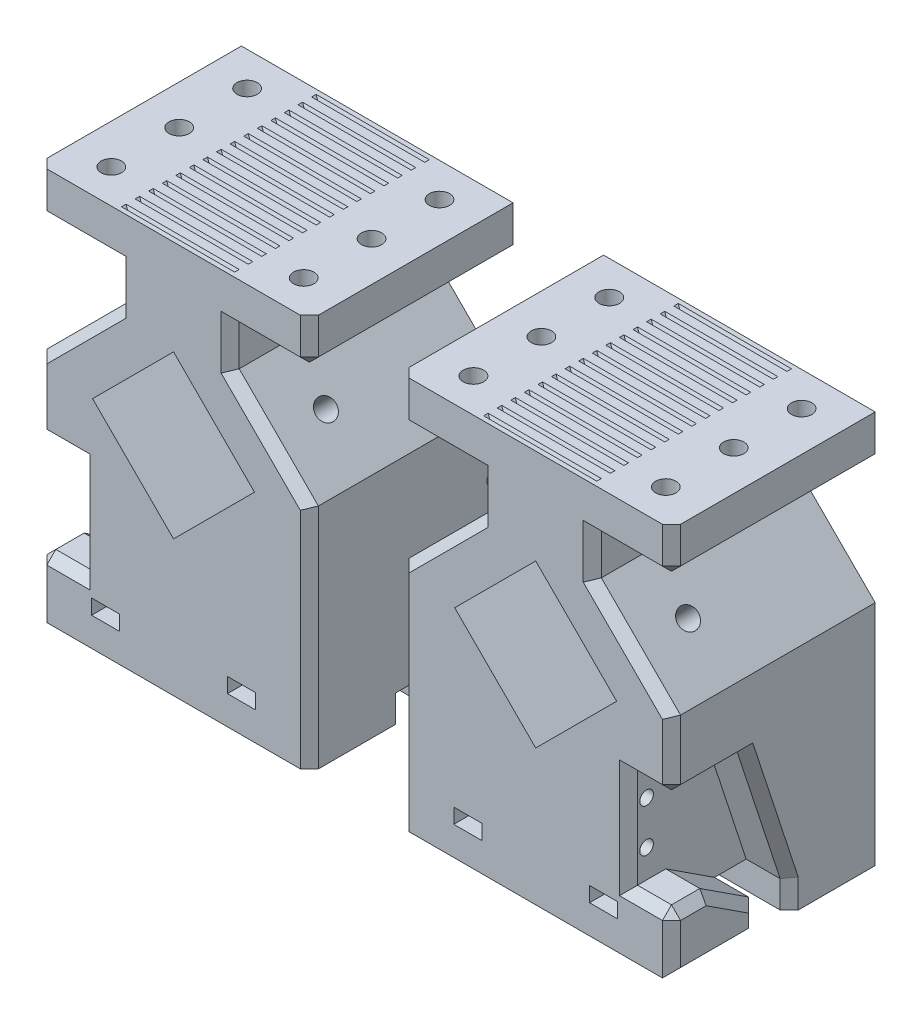
SolidWorks part; units mm, degrees
material "ABS"
ref_plane "Front Plane" through (0, 0, 0) normal (0, 0, 1) x (1, 0, 0)
ref_plane "Top Plane" through (0, 0, 0) normal (0, 1, 0) x (1, 0, 0)
ref_plane "Right Plane" through (0, 0, 0) normal (1, 0, 0) x (0, 0, -1)
sketch "Sketch1" plane through (0, 0, 0) normal (0, 0, 1) x (1, 0, 0)
  line L0 (-30, 25.15) -> (-12.5, 42.65)
  line L2 (30, 25.15) -> (30, -25.15)
  line L3 (30, -25.15) -> (-30, -25.15)
  line L4 (-30, 25.15) -> (-30, -25.15)
  line L5 (30, 25.15) -> (-30, -25.15) construction
  line L6 (30, -25.15) -> (-30, 25.15) construction
  line L7 (30, 25.15) -> (12.5, 42.65)
  line L8 (12.5, 42.65) -> (12.5, 51.65)
  line L9 (-12.5, 42.65) -> (-12.5, 51.65)
  line L10 (-12.5, 51.65) -> (12.5, 51.65) construction
  line L11 (-12.5, 51.65) -> (-30, 51.65)
  line L12 (-30, 51.65) -> (-30, 61.65)
  line L13 (-30, 61.65) -> (30, 61.65)
  line L14 (30, 61.65) -> (30, 51.65)
  line L15 (30, 51.65) -> (12.5, 51.65)
  point P0 (0, 0)
  dimension "D1" = 60
  dimension "D2" = 50.3
  dimension "D3" = 17.5
  dimension "D4" = 17.5
  dimension "D5" = 17.5
  dimension "D6" = 17.5
  dimension "D7" = 9
  dimension "D8" = 10
  dimension "D9" = 25.15
extrude "Boss-Extrude1" add sketch "Sketch1" along normal blind 45
sketch "Sketch2" plane through (0, 0, 45) normal (0, 0, 1) x (1, 0, 0)
  line L0 (0, 40.6296) -> (-17.8898, 22.7398)
  line L1 (-17.8898, 22.7398) -> (0, 4.85)
  line L2 (0, 4.85) -> (17.8898, 22.7398)
  line L3 (17.8898, 22.7398) -> (0, 40.6296)
  line L4 (0, 40.6296) -> (0, 0) construction
  line L5 (-30, -25.15) -> (30, -25.15) construction
  dimension "D1" = 25.3
  dimension "D2" = 25.3
  dimension "D3" = 30
extrude "Cut-Extrude1" cut sketch "Sketch2" against normal blind 25
sketch "Sketch3" plane through (0, -25.15, 0) normal (0, -1, 0) x (1, 0, 0)
  line L0 (-30, 26) -> (30, 26)
  line L1 (-30, 45) -> (-30, 0) construction
  line L2 (30, 45) -> (30, 0) construction
  line L3 (30, 26) -> (30, 19)
  line L4 (30, 19) -> (4.5, 19)
  line L5 (4.5, 19) -> (4.5, 3)
  line L6 (4.5, 3) -> (-4.5, 3)
  line L7 (-4.5, 3) -> (-4.5, 19)
  line L8 (-4.5, 19) -> (-30, 19)
  line L9 (-30, 19) -> (-30, 26)
  line L10 (0, 0) -> (0, 45) construction
  line L11 (-30, 0) -> (30, 0) construction
  line L12 (-30, 45) -> (30, 45) construction
  point P17 (0, 3)
  dimension "D1" = 9
  dimension "D2" = 7
  dimension "D3" = 16
  dimension "D4" = 19
extrude "Cut-Extrude2" cut sketch "Sketch3" against normal blind 6
sketch "Sketch4" plane through (-30, 0, 0) normal (-1, 0, 0) x (0, 0, 1)
  line L0 (45, 25.15) -> (45, -25.15) construction
  line L1 (45, 9.85) -> (28.5, 9.85)
  line L2 (45, 9.85) -> (45, -12.15)
  line L3 (45, -12.15) -> (36.75, -12.15)
  line L5 (45, -25.15) -> (26, -25.15) construction
  line L6 (26, -19.15) -> (36.75, -12.15)
  line L7 (19, -19.15) -> (28.5, 9.85)
  line L8 (26, -19.15) -> (19, -19.15)
  dimension "D1" = 16.5
  dimension "D2" = 13
  dimension "D3" = 22
  dimension "D4" = 8.25
extrude "Cut-Extrude4" cut sketch "Sketch4" against normal blind 9.5
sketch "Sketch5" plane through (0, 0, 0) normal (1, 0, 0) x (0, 0, -1)
  line L0 (-3, -19.15) -> (-3, 9.5665)
  line L1 (-4.0851, 13.008) -> (-11.2085, 23.1813)
  line L2 (-16.1234, 25.7398) -> (-20, 25.7398)
  line L3 (-20, 40.6296) -> (-20, 22.7398) construction
  line L4 (-20, 25.7398) -> (-20, 19.7398)
  line L5 (-20, 22.7398) -> (-20, 4.85) construction
  line L6 (-20, 19.7398) -> (-19.2468, 19.7398)
  line L7 (-14.3319, 17.1813) -> (-10.0851, 11.1162)
  line L8 (-9, 7.6747) -> (-9, -19.15)
  line L9 (-19, -19.15) -> (-3, -19.15) construction
  line L10 (-9, -19.15) -> (-3, -19.15)
  line L11 (-20, 22.7398) -> (-45, 22.7398) construction
  arc A0 (-3, 9.5665) -> (-4.0851, 13.008) centre (-9, 9.5665) ccw
  arc A1 (-10.0851, 11.1162) -> (-9, 7.6747) centre (-15, 7.6747) cw
  arc A2 (-11.2085, 23.1813) -> (-16.1234, 25.7398) centre (-16.1234, 19.7398) ccw
  arc A3 (-19.2468, 19.7398) -> (-14.3319, 17.1813) centre (-19.2468, 13.7398) cw
  point P15 (-19.6234, 19.7398)
  point P24 (-13, 25.7398)
  dimension "D7" = 6
  dimension "D1" = 6
  dimension "D2" = 6
  dimension "D3" = 6
  dimension "D4" = 3
  dimension "D5" = 145
  dimension "D6" = 7
extrude "Cut-Extrude5" cut sketch "Sketch5" against normal mid plane 9
fillet "Fillet1" radius 6 1 edges at (0, -19.15, 9)
ref_plane "Plane1" through (11.5, 0, 0) normal (1, 0, 0) x (0, 0, -1)
sketch "Sketch7" plane through (11.5, 0, 0) normal (1, 0, 0) x (0, 0, -1)
  line L0 (-1, 61.65) -> (-2, 61.65)
  line L1 (-45, 61.65) -> (0, 61.65) construction
  line L2 (-2, 61.65) -> (-1.5, 60.65)
  line L3 (-1.5, 60.65) -> (-1, 61.65)
  line L4 (-1.5, 60.65) -> (-1.5, 61.65) construction
  line L5 (-5, 61.65) -> (-4.5, 60.65)
  line L6 (-4, 61.65) -> (-5, 61.65)
  line L7 (-4.5, 60.65) -> (-4, 61.65)
  line L8 (-8, 61.65) -> (-7.5, 60.65)
  line L9 (-7, 61.65) -> (-8, 61.65)
  line L10 (-7.5, 60.65) -> (-7, 61.65)
  line L11 (-11, 61.65) -> (-10.5, 60.65)
  line L12 (-10, 61.65) -> (-11, 61.65)
  line L13 (-10.5, 60.65) -> (-10, 61.65)
  line L14 (-14, 61.65) -> (-13.5, 60.65)
  line L15 (-13, 61.65) -> (-14, 61.65)
  line L16 (-13.5, 60.65) -> (-13, 61.65)
  line L17 (-17, 61.65) -> (-16.5, 60.65)
  line L18 (-16, 61.65) -> (-17, 61.65)
  line L19 (-16.5, 60.65) -> (-16, 61.65)
  line L20 (-20, 61.65) -> (-19.5, 60.65)
  line L21 (-19, 61.65) -> (-20, 61.65)
  line L22 (-19.5, 60.65) -> (-19, 61.65)
  line L23 (-23, 61.65) -> (-22.5, 60.65)
  line L24 (-22, 61.65) -> (-23, 61.65)
  line L25 (-22.5, 60.65) -> (-22, 61.65)
  line L26 (-26, 61.65) -> (-25.5, 60.65)
  line L27 (-25, 61.65) -> (-26, 61.65)
  line L28 (-25.5, 60.65) -> (-25, 61.65)
  line L29 (-29, 61.65) -> (-28.5, 60.65)
  line L30 (-28, 61.65) -> (-29, 61.65)
  line L31 (-28.5, 60.65) -> (-28, 61.65)
  line L32 (-32, 61.65) -> (-31.5, 60.65)
  line L33 (-31, 61.65) -> (-32, 61.65)
  line L34 (-31.5, 60.65) -> (-31, 61.65)
  line L35 (-35, 61.65) -> (-34.5, 60.65)
  line L36 (-34, 61.65) -> (-35, 61.65)
  line L37 (-34.5, 60.65) -> (-34, 61.65)
  line L38 (-38, 61.65) -> (-37.5, 60.65)
  line L39 (-37, 61.65) -> (-38, 61.65)
  line L40 (-37.5, 60.65) -> (-37, 61.65)
  line L41 (-41, 61.65) -> (-40.5, 60.65)
  line L42 (-40, 61.65) -> (-41, 61.65)
  line L43 (-40.5, 60.65) -> (-40, 61.65)
  line L44 (-44, 61.65) -> (-43.5, 60.65)
  line L45 (-43, 61.65) -> (-44, 61.65)
  line L46 (-43.5, 60.65) -> (-43, 61.65)
  line L47 (-47, 61.65) -> (-46.5, 60.65)
  line L48 (-46, 61.65) -> (-47, 61.65)
  line L49 (-46.5, 60.65) -> (-46, 61.65)
  line L50 (-50, 61.65) -> (-49.5, 60.65)
  line L51 (-49, 61.65) -> (-50, 61.65)
  line L52 (-49.5, 60.65) -> (-49, 61.65)
  line L53 (-53, 61.65) -> (-52.5, 60.65)
  line L54 (-52, 61.65) -> (-53, 61.65)
  line L55 (-52.5, 60.65) -> (-52, 61.65)
  line L56 (-56, 61.65) -> (-55.5, 60.65)
  line L57 (-55, 61.65) -> (-56, 61.65)
  line L58 (-55.5, 60.65) -> (-55, 61.65)
  line L59 (-59, 61.65) -> (-58.5, 60.65)
  line L60 (-58, 61.65) -> (-59, 61.65)
  line L61 (-58.5, 60.65) -> (-58, 61.65)
  line L62 (-62, 61.65) -> (-61.5, 60.65)
  line L63 (-61, 61.65) -> (-62, 61.65)
  line L64 (-61.5, 60.65) -> (-61, 61.65)
  line L65 (-65, 61.65) -> (-64.5, 60.65)
  line L66 (-64, 61.65) -> (-65, 61.65)
  line L67 (-64.5, 60.65) -> (-64, 61.65)
  dimension "D1" = 1
  dimension "D2" = 1
  dimension "D3" = 1
  dimension "D5" = 3
  dimension "D4" = 22
extrude "Cut-Extrude7" cut sketch "Sketch7" against normal blind 23
chamfer "Chamfer1" distance 1 angle 45 30 edges at (-11.5, 61.65, 43.5) (-11.5, 61.65, 40.5) (-11.5, 61.65, 37.5) (-11.5, 61.65, 34.5) (-11.5, 61.65, 31.5) (-11.5, 61.65, 28.5) (-11.5, 61.65, 25.5) (-11.5, 61.65, 22.5) (-11.5, 61.65, 19.5) (-11.5, 61.65, 16.5) (-11.5, 61.65, 13.5) (-11.5, 61.65, 10.5) (-11.5, 61.65, 7.5) (-11.5, 61.65, 4.5) (-11.5, 61.65, 1.5) (11.5, 61.65, 43.5) (11.5, 61.65, 40.5) (11.5, 61.65, 37.5) (11.5, 61.65, 34.5) (11.5, 61.65, 31.5) (11.5, 61.65, 28.5) (11.5, 61.65, 25.5) (11.5, 61.65, 22.5) (11.5, 61.65, 19.5) (11.5, 61.65, 16.5) (11.5, 61.65, 13.5) (11.5, 61.65, 10.5) (11.5, 61.65, 7.5) (11.5, 61.65, 4.5) (11.5, 61.65, 1.5)
sketch "Sketch8" plane through (0, 61.65, 0) normal (0, 1, 0) x (1, 0, 0)
  line L0 (0, 0) -> (0, -45) construction
  line L1 (30, -45) -> (-30, -45) construction
  line L3 (21.25, -7.5) -> (-21.25, -7.5) construction
  line L4 (21.25, -7.5) -> (21.25, -37.5) construction
  line L5 (21.25, -37.5) -> (-21.25, -37.5) construction
  line L6 (-21.25, -7.5) -> (-21.25, -37.5) construction
  line L7 (21.25, -7.5) -> (-21.25, -37.5) construction
  line L8 (21.25, -37.5) -> (-21.25, -7.5) construction
  circle A0 centre (-21.25, -37.5) radius 2.25
  circle A1 centre (-21.25, -22.5) radius 2.25
  circle A2 centre (-21.25, -7.5) radius 2.25
  circle A3 centre (21.25, -7.5) radius 2.25
  circle A4 centre (21.25, -22.5) radius 2.25
  circle A5 centre (21.25, -37.5) radius 2.25
  point P5 (0, -22.5)
  dimension "D3" = 4.5
  dimension "D4" = 4.5
  dimension "D5" = 4.5
  dimension "D6" = 4.5
  dimension "D7" = 4.5
  dimension "D8" = 4.5
  dimension "D1" = 30
  dimension "D2" = 42.5
extrude "Cut-Extrude8" cut sketch "Sketch8" against normal blind 10
sketch "Sketch9" plane through (0, 51.65, 0) normal (0, -1, 0) x (1, 0, 0)
  line L1 (-25.2915, 22.5) -> (-23.2707, 19)
  line L2 (-23.2707, 19) -> (-19.2293, 19)
  line L3 (-19.2293, 19) -> (-17.2085, 22.5)
  line L4 (-17.2085, 22.5) -> (-19.2293, 26)
  line L5 (-19.2293, 26) -> (-23.2707, 26)
  line L6 (-23.2707, 26) -> (-25.2915, 22.5)
  line L7 (-25.2915, 37.5) -> (-23.2707, 34)
  line L8 (-23.2707, 34) -> (-19.2293, 34)
  line L9 (-19.2293, 34) -> (-17.2085, 37.5)
  line L10 (-17.2085, 37.5) -> (-19.2293, 41)
  line L11 (-19.2293, 41) -> (-23.2707, 41)
  line L12 (-23.2707, 41) -> (-25.2915, 37.5)
  line L13 (-25.2915, 7.5) -> (-23.2707, 4)
  line L14 (-23.2707, 4) -> (-19.2293, 4)
  line L15 (-19.2293, 4) -> (-17.2085, 7.5)
  line L16 (-17.2085, 7.5) -> (-19.2293, 11)
  line L17 (-19.2293, 11) -> (-23.2707, 11)
  line L18 (-23.2707, 11) -> (-25.2915, 7.5)
  line L19 (25.2915, 7.5) -> (23.2707, 11)
  line L20 (23.2707, 11) -> (19.2293, 11)
  line L21 (19.2293, 11) -> (17.2085, 7.5)
  line L22 (17.2085, 7.5) -> (19.2293, 4)
  line L23 (19.2293, 4) -> (23.2707, 4)
  line L24 (23.2707, 4) -> (25.2915, 7.5)
  line L25 (25.4834, 22.6108) -> (23.4627, 26.1108)
  line L26 (23.4627, 26.1108) -> (19.4212, 26.1108)
  line L27 (19.4212, 26.1108) -> (17.4005, 22.6108)
  line L28 (17.4005, 22.6108) -> (19.4212, 19.1108)
  line L29 (19.4212, 19.1108) -> (23.4627, 19.1108)
  line L30 (23.4627, 19.1108) -> (25.4834, 22.6108)
  line L31 (25.4834, 37.6108) -> (23.4627, 41.1108)
  line L32 (23.4627, 41.1108) -> (19.4212, 41.1108)
  line L33 (19.4212, 41.1108) -> (17.4005, 37.6108)
  line L34 (17.4005, 37.6108) -> (19.4212, 34.1108)
  line L35 (19.4212, 34.1108) -> (23.4627, 34.1108)
  line L36 (23.4627, 34.1108) -> (25.4834, 37.6108)
  circle A0 centre (-21.25, 22.5) radius 3.5 construction
  circle A1 centre (-21.25, 37.5) radius 3.5 construction
  circle A2 centre (-21.25, 7.5) radius 3.5 construction
  circle A3 centre (21.25, 7.5) radius 3.5 construction
  circle A4 centre (21.4419, 22.6108) radius 3.5 construction
  circle A5 centre (21.4419, 37.6108) radius 3.5 construction
  dimension "D1" = 7
  dimension "D2" = 7
  dimension "D3" = 7
  dimension "D4" = 7
  dimension "D5" = 7
  dimension "D6" = 7
extrude "Cut-Extrude9" cut sketch "Sketch9" against normal blind 3.2
sketch "Sketch10" plane through (0, -25.15, 0) normal (0, -1, 0) x (1, 0, 0)
  line L0 (-30, 45) -> (-30, 26) construction
  line L1 (15, 7.5) -> (-15, 7.5) construction
  line L2 (15, 7.5) -> (15, 37.5) construction
  line L3 (15, 37.5) -> (-15, 37.5) construction
  line L4 (-15, 7.5) -> (-15, 37.5) construction
  line L5 (15, 7.5) -> (-15, 37.5) construction
  line L6 (15, 37.5) -> (-15, 7.5) construction
  line L7 (-30, 45) -> (30, 45) construction
  circle A0 centre (-15, 37.5) radius 1.75
  circle A1 centre (-15, 7.5) radius 1.75
  circle A2 centre (15, 7.5) radius 1.75
  circle A3 centre (15, 37.5) radius 1.75
  point P0 (0, 22.5)
  dimension "D5" = 3.5
  dimension "D6" = 3.5
  dimension "D7" = 3.5
  dimension "D8" = 3.5
  dimension "D1" = 30
  dimension "D2" = 22.5
  dimension "D3" = 30
  dimension "D4" = 30
extrude "Cut-Extrude10" cut sketch "Sketch10" against normal blind 20
ref_plane "Plane2" through (0, -18.8, 0) normal (0, -1, 0) x (-1, 0, 0)
sketch "Sketch11" plane through (0, -18.8, 0) normal (0, -1, 0) x (-1, 0, 0)
  line L0 (30, -45) -> (-30, -45) construction
  line L1 (-11.9, -45) -> (-18.1, -45)
  line L2 (-11.9, -45) -> (-11.9, -33)
  line L3 (-11.9, -33) -> (-18.1, -33)
  line L4 (-18.1, -45) -> (-18.1, -33)
  line L5 (30, 0) -> (-30, 0) construction
  line L6 (11.9, -45) -> (18.1, -45)
  line L7 (11.9, -45) -> (11.9, -33)
  line L8 (11.9, -33) -> (18.1, -33)
  line L9 (18.1, -45) -> (18.1, -33)
  line L10 (11.9, 0) -> (18.1, 0)
  line L11 (11.9, 0) -> (11.9, -12)
  line L12 (11.9, -12) -> (18.1, -12)
  line L13 (18.1, 0) -> (18.1, -12)
  line L14 (-30, -45) -> (-30, -26) construction
  line L15 (-18.1, 0) -> (-11.9, 0)
  line L16 (-18.1, 0) -> (-18.1, -12)
  line L17 (-18.1, -12) -> (-11.9, -12)
  line L18 (-11.9, 0) -> (-11.9, -12)
  line L19 (30, -45) -> (30, -26) construction
  dimension "D1" = 11.9
  dimension "D2" = 6.2
  dimension "D3" = 12
  dimension "D4" = 11.9
  dimension "D5" = 6.2
  dimension "D6" = 12
extrude "Cut-Extrude11" cut sketch "Sketch11" against normal blind 3.3
sketch "Sketch12" plane through (0, -18.8, 0) normal (0, -1, 0) x (-1, 0, 0)
  line L0 (-15, -7.5) -> (-15, -4.0359) construction
  line L1 (15, -34.0359) -> (12, -35.7679)
  line L2 (12, -35.7679) -> (12, -39.2321)
  line L3 (12, -39.2321) -> (15, -40.9641)
  line L4 (15, -40.9641) -> (18, -39.2321)
  line L5 (18, -39.2321) -> (18, -35.7679)
  line L6 (18, -35.7679) -> (15, -34.0359)
  line L7 (15, -10.9641) -> (18, -9.2321)
  line L8 (18, -9.2321) -> (18, -5.7679)
  line L9 (18, -5.7679) -> (15, -4.0359)
  line L10 (15, -4.0359) -> (12, -5.7679)
  line L11 (12, -5.7679) -> (12, -9.2321)
  line L12 (12, -9.2321) -> (15, -10.9641)
  line L13 (-15, -10.9641) -> (-12, -9.2321)
  line L14 (-12, -9.2321) -> (-12, -5.7679)
  line L15 (-12, -5.7679) -> (-15, -4.0359)
  line L16 (-15, -4.0359) -> (-18, -5.7679)
  line L17 (-18, -5.7679) -> (-18, -9.2321)
  line L18 (-18, -9.2321) -> (-15, -10.9641)
  line L19 (-15, -34.0359) -> (-18, -35.7679)
  line L20 (-18, -35.7679) -> (-18, -39.2321)
  line L21 (-18, -39.2321) -> (-15, -40.9641)
  line L22 (-15, -40.9641) -> (-12, -39.2321)
  line L23 (-12, -39.2321) -> (-12, -35.7679)
  line L24 (-12, -35.7679) -> (-15, -34.0359)
  line L25 (15, -7.5) -> (15, -4.0359) construction
  line L26 (-15, -37.5) -> (-15, -34.0359) construction
  line L27 (15, -37.5) -> (15, -34.0359) construction
  circle A0 centre (15, -37.5) radius 3 construction
  circle A1 centre (15, -7.5) radius 3 construction
  circle A2 centre (-15, -7.5) radius 3 construction
  circle A3 centre (-15, -37.5) radius 3 construction
  dimension "D1" = 6
  dimension "D2" = 6
  dimension "D3" = 6
  dimension "D4" = 6
extrude "Cut-Extrude12" cut sketch "Sketch12" along normal blind 1.5
sketch "Sketch13" plane through (-20.5, 0, 0) normal (-1, 0, 0) x (0, 0, 1)
  line L0 (41, -5.9) -> (41, 3.6) construction
  line L1 (45, -12.15) -> (45, 9.85) construction
  line L2 (36.75, -12.15) -> (45, -12.15) construction
  circle A0 centre (41, -5.9) radius 1.5
  circle A1 centre (41, 3.6) radius 1.5
  dimension "D4" = 3
  dimension "D5" = 3
  dimension "D1" = 4
  dimension "D2" = 9.5
  dimension "D3" = 6.25
extrude "Cut-Extrude13" cut sketch "Sketch13" against normal blind 15
sketch "Sketch14" plane through (-27.575, 27.575, 0) normal (-0.7071, 0.7071, 0) x (0, 0, 1)
  line L0 (45, 21.3193) -> (45, -3.4295) construction
  line L1 (45, -3.4295) -> (0, -3.4295) construction
  circle A0 centre (32.5, 9.0705) radius 2.25
  dimension "D1" = 12.5
  dimension "D2" = 12.5
  dimension "D3" = 4.5
extrude "Cut-Extrude14" cut sketch "Sketch14" against normal blind 15
sketch "Sketch15" plane through (-20.3148, 20.3148, 0) normal (0.7071, -0.7071, 0) x (0, 0, -1)
  line L0 (-32.5, 9.0705) -> (-28.4585, 9.0705) construction
  line L1 (-28.4585, 9.0705) -> (-30.4793, 12.5705)
  line L2 (-30.4793, 12.5705) -> (-34.5207, 12.5705)
  line L3 (-34.5207, 12.5705) -> (-36.5415, 9.0705)
  line L4 (-36.5415, 9.0705) -> (-34.5207, 5.5705)
  line L5 (-34.5207, 5.5705) -> (-30.4793, 5.5705)
  line L6 (-30.4793, 5.5705) -> (-28.4585, 9.0705)
  circle A0 centre (-32.5, 9.0705) radius 3.5 construction
  dimension "D1" = 7
extrude "Cut-Extrude15" cut sketch "Sketch15" against normal blind 3.5
mirror "Mirror1" about plane through (0, 0, 0) normal (1, 0, 0) of "Cut-Extrude14", "Cut-Extrude15"
sketch "Sketch16" plane through (30, 0, 0) normal (1, 0, 0) x (0, 0, -1)
  line L0 (-4, 11.25) -> (-4, -11.25) construction
  line L1 (-19, -25.15) -> (0, -25.15) construction
  line L2 (0, -25.15) -> (0, 25.15) construction
  circle A0 centre (-4, 11.25) radius 1.8
  circle A1 centre (-4, -11.25) radius 1.8
  dimension "D4" = 3.6
  dimension "D5" = 3.6
  dimension "D1" = 13.9
  dimension "D2" = 22.5
  dimension "D3" = 4
extrude "Cut-Extrude23" cut sketch "Sketch16" against normal blind 20
sketch "Sketch17" plane through (0, 0, 0) normal (0, 0, -1) x (-1, 0, 0)
  line L0 (30, -25.15) -> (-30, -25.15) construction
  line L1 (-23.65, -8.15) -> (-20.35, -8.15)
  line L2 (-23.65, -8.15) -> (-23.65, -14.35)
  line L3 (-23.65, -14.35) -> (-20.35, -14.35)
  line L4 (-20.35, -8.15) -> (-20.35, -14.35)
  line L5 (-23.65, 14.35) -> (-20.35, 14.35)
  line L6 (-23.65, 14.35) -> (-23.65, 8.15)
  line L7 (-23.65, 8.15) -> (-20.35, 8.15)
  line L8 (-20.35, 14.35) -> (-20.35, 8.15)
  line L9 (-30, -25.15) -> (-30, 25.15) construction
  point P12 (-22, -8.15)
  dimension "D1" = 10.8
  dimension "D2" = 6.35
  dimension "D3" = 6.2
  dimension "D4" = 6.2
  dimension "D5" = 3.3
  dimension "D6" = 16.3
extrude "Cut-Extrude24" cut sketch "Sketch17" against normal blind 8
sketch "Sketch18" plane through (23.65, 0, 0) normal (-1, 0, 0) x (0, 0, 1)
  line L0 (0.8246, -11.25) -> (4.1512, -11.25) construction
  line L1 (0.8246, 11.25) -> (2.4123, 8.5)
  line L2 (2.4123, 8.5) -> (5.5877, 8.5)
  line L3 (5.5877, 8.5) -> (7.1754, 11.25)
  line L4 (7.1754, 11.25) -> (5.5877, 14)
  line L5 (5.5877, 14) -> (2.4123, 14)
  line L6 (2.4123, 14) -> (0.8246, 11.25)
  line L7 (0.8246, -11.25) -> (2.4123, -14)
  line L8 (2.4123, -14) -> (5.5877, -14)
  line L9 (5.5877, -14) -> (7.1754, -11.25)
  line L10 (7.1754, -11.25) -> (5.5877, -8.5)
  line L11 (5.5877, -8.5) -> (2.4123, -8.5)
  line L12 (2.4123, -8.5) -> (0.8246, -11.25)
  line L13 (4, 11.25) -> (1.0281, 11.25) construction
  circle A0 centre (4, 11.25) radius 2.75 construction
  circle A1 centre (4, -11.25) radius 2.75 construction
  dimension "D1" = 5.5
  dimension "D2" = 5.5
extrude "Cut-Extrude25" cut sketch "Sketch18" against normal blind 1.5
chamfer "Chamfer2" distance 2 angle 45 23 edges at (-30, -25.15, 35.5) (-30, -22.15, 26) (-30, -15.65, 31.375) (-30, -12.15, 40.875) (-30, -18.65, 45) (-30, -22.15, 19) (-30, -4.65, 23.75) (-30, 9.85, 36.75) (-25.25, -12.15, 45) (-20.5, -1.15, 45) (-25.25, 9.85, 45) (-30, 17.5, 45) (-30, 51.65, 22.5) (-21.25, 33.9, 45) (-12.5, 47.15, 45) (-21.25, 51.65, 45) (-30, 56.65, 45) (30, 0, 45) (21.25, 33.9, 45) (12.5, 47.15, 45) (21.25, 51.65, 45) (30, 56.65, 45) (30, 51.65, 22.5)
ref_plane "Plane3" through (40, 0, 0) normal (1, 0, 0) x (0, 0, -1)
mirror "Mirror4" about plane through (40, 0, 0) normal (1, 0, 0) of bodies 119
